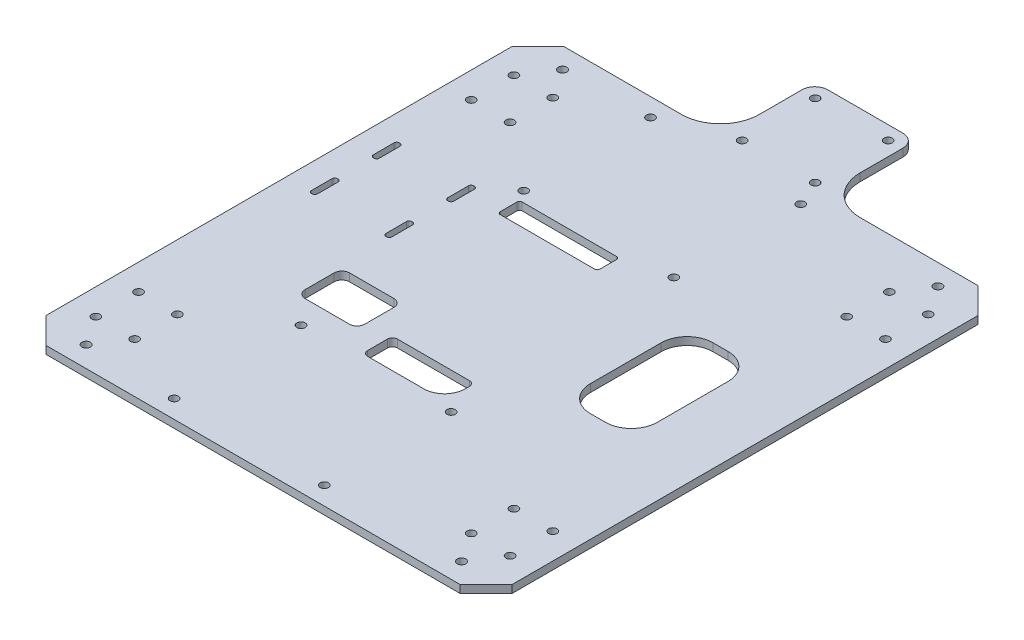
SolidWorks part; units mm, degrees
ref_plane "Front Plane" through (0, 0, 0) normal (0, 0, 1) x (1, 0, 0)
ref_plane "Top Plane" through (0, 0, 0) normal (0, 1, 0) x (1, 0, 0)
ref_plane "Right Plane" through (0, 0, 0) normal (1, 0, 0) x (0, 0, -1)
sketch "Sketch1" plane through (0, 0, 0) normal (0, 1, 0) x (1, 0, 0)
  line L0 (0, 132.1036) -> (0, -142.6838) construction
  line L1 (-90, 100) -> (90, 100)
  line L2 (-90, 100) -> (-90, -100)
  line L3 (-90, -100) -> (90, -100)
  line L4 (90, 100) -> (90, -100)
  line L5 (-90, 100) -> (90, -100) construction
  line L6 (-90, -100) -> (90, 100) construction
  line L7 (0, -55) -> (0, 55) construction
  line L8 (-189.9448, 0) -> (195.6261, 0) construction
  line L9 (18.5, 87.6829) -> (18.5, -193.4849) construction
  line L10 (-39.5, 87.6829) -> (-39.5, -193.4849) construction
  circle A0 centre (18.5, 93) radius 1.6
  circle A1 centre (18.5, 44) radius 1.6
  circle A2 centre (-39.5, 93) radius 1.6
  circle A3 centre (-39.5, 44) radius 1.6
  circle A9 centre (20.5, -93) radius 1.6
  circle A10 centre (20.5, -44) radius 1.6
  circle A11 centre (-37.5, -44) radius 1.6
  circle A12 centre (-37.5, -93) radius 1.6
  point P0 (0, 0)
  dimension "D3" = 58
  dimension "D4" = 3.2
  dimension "D5" = 3.2
  dimension "D6" = 49
  dimension "D7" = 7
  dimension "D8" = 58
  dimension "D9" = 18.5
  dimension "D10" = 18.5
  dimension "D11" = 39.5
  dimension "D12" = 49
  dimension "D13" = 3.2
  dimension "D14" = 3.2
  dimension "D15" = 3.2
  dimension "D16" = 7
  dimension "D17" = 2
  dimension "D18" = 3.2
  dimension "D19" = 49
  dimension "D20" = 20.5
  dimension "D21" = 58
  dimension "D22" = 3.2
  dimension "D23" = 3.2
  dimension "D24" = 49
  dimension "D25" = 58
  dimension "D26" = 37.5
  dimension "D1" = 180
  dimension "D2" = 200
extrude "Boss-Extrude1" add sketch "Sketch1" along normal blind 3
sketch "Sketch2" plane through (0, 3, 0) normal (0, 1, 0) x (1, 0, 0)
  line L0 (-162.8834, 0) -> (150.0475, 0) construction
  line L1 (0, 129.9084) -> (0, -141.4164) construction
  line L3 (-14.1809, -29.9956) -> (13.5, -29.9956)
  line L4 (-16.1809, -31.9956) -> (-16.1809, -39.5537)
  line L5 (-14.1809, -41.5537) -> (7.5, -41.5537)
  line L6 (15.5, -31.9956) -> (15.5, -33.5537)
  line L7 (-36.0134, 39.9424) -> (0.4565, 39.9424)
  line L8 (-37.0134, 38.9424) -> (-37.0134, 32.4822)
  line L9 (-36.0134, 31.4822) -> (0.4565, 31.4822)
  line L10 (1.4565, 38.9424) -> (1.4565, 32.4822)
  line L11 (-45.6227, -17.1125) -> (-28.5341, -17.1125)
  line L12 (-48.6227, -20.1125) -> (-48.6227, -31.2965)
  line L13 (-45.6227, -34.2965) -> (-28.5341, -34.2965)
  line L14 (-25.5341, -20.1125) -> (-25.5341, -31.2965)
  arc A0 (15.5, -31.9956) -> (13.5, -29.9956) centre (13.5, -31.9956) ccw
  arc A1 (-14.1809, -41.5537) -> (-16.1809, -39.5537) centre (-14.1809, -39.5537) cw
  arc A2 (-16.1809, -31.9956) -> (-14.1809, -29.9956) centre (-14.1809, -31.9956) cw
  arc A3 (7.5, -41.5537) -> (15.5, -33.5537) centre (7.5, -33.5537) ccw
  arc A4 (0.4565, 39.9424) -> (1.4565, 38.9424) centre (0.4565, 38.9424) cw
  arc A5 (0.4565, 31.4822) -> (1.4565, 32.4822) centre (0.4565, 32.4822) ccw
  arc A6 (-36.0134, 31.4822) -> (-37.0134, 32.4822) centre (-36.0134, 32.4822) cw
  arc A7 (-37.0134, 38.9424) -> (-36.0134, 39.9424) centre (-36.0134, 38.9424) cw
  circle A8 centre (20.5, -44) radius 1.6 construction
  arc A9 (-25.5341, -20.1125) -> (-28.5341, -17.1125) centre (-28.5341, -20.1125) ccw
  arc A10 (-28.5341, -34.2965) -> (-25.5341, -31.2965) centre (-28.5341, -31.2965) ccw
  arc A11 (-45.6227, -34.2965) -> (-48.6227, -31.2965) centre (-45.6227, -31.2965) cw
  arc A12 (-48.6227, -20.1125) -> (-45.6227, -17.1125) centre (-45.6227, -20.1125) cw
  dimension "D1" = 2
  dimension "D2" = 8
  dimension "D3" = 1
  dimension "D5" = 5
  dimension "D4" = 3
extrude "Cut-Extrude1" cut sketch "Sketch2" against normal up to surface (3 mm away) up to face at (0, 0, 0)
sketch "Sketch3" plane through (0, 3, 0) normal (0, 1, 0) x (1, 0, 0)
  line L0 (90, -100) -> (90, 100) construction
  line L1 (0, 125.5002) -> (0, -134.5016) construction
  line L2 (-137.7639, 0) -> (136.9662, 0) construction
  line L3 (-55, 0) -> (55, 0) construction
  line L4 (90, 100) -> (-90, 100) construction
  line L5 (80, 80.75) -> (80, 64.25) construction
  line L6 (80, 72.5) -> (90.3323, 72.5) construction
  line L7 (0, -55) -> (0, 55) construction
  line L8 (-80, 80.75) -> (-80, 64.25) construction
  line L9 (-80, 72.5) -> (-90.3323, 72.5) construction
  line L10 (80, -80.75) -> (80, -64.25) construction
  line L11 (80, -72.5) -> (90.3323, -72.5) construction
  line L12 (-80, -80.75) -> (-80, -64.25) construction
  line L13 (-80, -72.5) -> (-90.3323, -72.5) construction
  line L15 (-90, 100) -> (-90, -100) construction
  circle A0 centre (80, 80.75) radius 1.6
  circle A1 centre (65, 80.75) radius 1.6
  circle A2 centre (65, 64.25) radius 1.6
  circle A3 centre (80, 64.25) radius 1.6
  circle A4 centre (-80, 64.25) radius 1.6
  circle A5 centre (-65, 64.25) radius 1.6
  circle A6 centre (-65, 80.75) radius 1.6
  circle A7 centre (-80, 80.75) radius 1.6
  circle A8 centre (-80, -80.75) radius 1.6
  circle A9 centre (-65, -80.75) radius 1.6
  circle A10 centre (-65, -64.25) radius 1.6
  circle A11 centre (-80, -64.25) radius 1.6
  circle A12 centre (80, -64.25) radius 1.6
  circle A13 centre (65, -64.25) radius 1.6
  circle A14 centre (65, -80.75) radius 1.6
  circle A15 centre (80, -80.75) radius 1.6
  dimension "D1" = 3.2
  dimension "D2" = 10
  dimension "D3" = 3.2
  dimension "D4" = 15
  dimension "D6" = 16.5
  dimension "D7" = 19.25
  dimension "D8" = 25
  dimension "D9" = 180.6646
  dimension "D5" = 2
sketch "Sketch4" plane through (0, 3, 0) normal (0, 1, 0) x (1, 0, 0)
  line L5 (0, 125.5002) -> (0, -134.5016) construction
  line L6 (0, 147.4469) -> (0, 90.5728) construction
  line L7 (20.1578, 117.1) -> (-23.4234, 117.1) construction
  line L12 (90, 100) -> (-90, 100) construction
  line L13 (-19.5, 100) -> (19.5, 100)
  line L14 (-19.5, 115) -> (-19.5, 136.5)
  line L15 (-19.5, 136.5) -> (19.5, 136.5)
  line L16 (19.5, 115) -> (19.5, 136.5)
  line L17 (34.5, 100) -> (19.5, 100)
  line L18 (-34.5, 100) -> (-19.5, 100)
  circle A0 centre (14.1, 103) radius 1.6
  circle A1 centre (-14.1, 103) radius 1.6
  circle A2 centre (14.1, 131.2) radius 1.6
  circle A3 centre (-14.1, 131.2) radius 1.6
  arc A4 (19.5, 115) -> (34.5, 100) centre (34.5, 115) ccw
  arc A5 (-19.5, 115) -> (-34.5, 100) centre (-34.5, 115) cw
  dimension "D4" = 3.2
  dimension "D5" = 15
  dimension "D7" = 28.2
  dimension "D9" = 28.2
  dimension "D2" = 36.5
  dimension "D3" = 19.5
extrude "Boss-Extrude2" add sketch "Sketch4" against normal up to surface (3 mm away) up to face at (-17.7785, 0, -35.7123)
extrude "Cut-Extrude2" cut sketch "Sketch3" against normal through all
sketch "Sketch5" plane through (0, 3, 0) normal (0, 1, 0) x (1, 0, 0)
  line L0 (-119.2376, 0) -> (145.54, 0) construction
  line L1 (-65.0269, 34.8534) -> (-65.0269, 2.369) construction
  line L2 (-79.5488, 35.9861) -> (-79.2488, 35.9861)
  line L3 (-80.5488, 34.9861) -> (-80.5488, 26.9861)
  line L4 (-79.5488, 25.9861) -> (-79.2488, 25.9861)
  line L5 (-78.2488, 34.9861) -> (-78.2488, 26.9861)
  line L6 (-80.5488, 35.9861) -> (-78.2488, 25.9861) construction
  line L7 (-80.5488, 25.9861) -> (-78.2488, 35.9861) construction
  line L8 (-82.0133, 19.0367) -> (-45.889, 19.0367) construction
  line L9 (-49.505, 34.9861) -> (-49.505, 26.9861)
  line L10 (-51.805, 34.9861) -> (-51.805, 26.9861)
  line L11 (-51.805, 3.0873) -> (-51.805, 11.0873)
  line L12 (-49.505, 3.0873) -> (-49.505, 11.0873)
  line L13 (-78.2488, 3.0873) -> (-78.2488, 11.0873)
  line L14 (-79.5488, 12.0873) -> (-79.2488, 12.0873)
  line L15 (-80.5488, 3.0873) -> (-80.5488, 11.0873)
  line L16 (-79.5488, 2.0873) -> (-79.2488, 2.0873)
  line L17 (-50.505, 25.9861) -> (-50.805, 25.9861)
  line L18 (-50.505, 35.9861) -> (-50.805, 35.9861)
  line L19 (-50.505, 2.0873) -> (-50.805, 2.0873)
  line L20 (-50.505, 12.0873) -> (-50.805, 12.0873)
  arc A0 (-79.2488, 35.9861) -> (-78.2488, 34.9861) centre (-79.2488, 34.9861) cw
  arc A1 (-80.5488, 34.9861) -> (-79.5488, 35.9861) centre (-79.5488, 34.9861) cw
  arc A2 (-78.2488, 26.9861) -> (-79.2488, 25.9861) centre (-79.2488, 26.9861) cw
  arc A3 (-80.5488, 26.9861) -> (-79.5488, 25.9861) centre (-79.5488, 26.9861) ccw
  arc A4 (-51.805, 26.9861) -> (-50.805, 25.9861) centre (-50.805, 26.9861) ccw
  arc A5 (-49.505, 26.9861) -> (-50.505, 25.9861) centre (-50.505, 26.9861) cw
  arc A6 (-50.805, 35.9861) -> (-51.805, 34.9861) centre (-50.805, 34.9861) ccw
  arc A7 (-49.505, 34.9861) -> (-50.505, 35.9861) centre (-50.505, 34.9861) ccw
  arc A8 (-49.505, 3.0873) -> (-50.505, 2.0873) centre (-50.505, 3.0873) cw
  arc A9 (-50.805, 2.0873) -> (-51.805, 3.0873) centre (-50.805, 3.0873) cw
  arc A10 (-49.505, 11.0873) -> (-50.505, 12.0873) centre (-50.505, 11.0873) ccw
  arc A11 (-51.805, 11.0873) -> (-50.805, 12.0873) centre (-50.805, 11.0873) cw
  arc A12 (-80.5488, 11.0873) -> (-79.5488, 12.0873) centre (-79.5488, 11.0873) cw
  arc A13 (-78.2488, 11.0873) -> (-79.2488, 12.0873) centre (-79.2488, 11.0873) ccw
  arc A14 (-80.5488, 3.0873) -> (-79.5488, 2.0873) centre (-79.5488, 3.0873) ccw
  arc A15 (-79.2488, 2.0873) -> (-78.2488, 3.0873) centre (-79.2488, 3.0873) ccw
  point P3 (-79.3988, 30.9861)
  point P61 (-79.3988, 7.0873)
  dimension "D3" = 1
  dimension "D1" = 10
  dimension "D2" = 2.3
extrude "Cut-Extrude3" cut sketch "Sketch5" against normal through all
sketch "Sketch6" plane through (0, 3, 0) normal (0, 1, 0) x (1, 0, 0)
  line L0 (90, 100) -> (34.5, 100) construction
  line L1 (0, 159.522) -> (0, -147.3384) construction
  line L2 (-99.4598, 0) -> (104.7768, 0) construction
  circle A0 centre (72.5, 92) radius 1.65
  circle A1 centre (80, 80.75) radius 1.6 construction
  circle A4 centre (-72.5, 92) radius 1.65
  circle A5 centre (72.5, -92) radius 1.65
  circle A6 centre (-72.5, -92) radius 1.65
  dimension "D1" = 3.3
  dimension "D2" = 7.5
  dimension "D3" = 8
extrude "Cut-Extrude4" cut sketch "Sketch6" against normal through all
sketch "Sketch7" plane through (0, 3, 0) normal (0, 1, 0) x (1, 0, 0)
  line L1 (47.9236, 29.7083) -> (53.7866, 29.7083)
  line L2 (37.9236, 19.7083) -> (37.9236, -7.6655)
  line L3 (47.9236, -17.6655) -> (53.7866, -17.6655)
  line L4 (63.7866, 19.7083) -> (63.7866, -7.6655)
  arc A0 (63.7866, 19.7083) -> (53.7866, 29.7083) centre (53.7866, 19.7083) ccw
  arc A1 (53.7866, -17.6655) -> (63.7866, -7.6655) centre (53.7866, -7.6655) ccw
  arc A2 (47.9236, -17.6655) -> (37.9236, -7.6655) centre (47.9236, -7.6655) cw
  arc A3 (37.9236, 19.7083) -> (47.9236, 29.7083) centre (47.9236, 19.7083) cw
  dimension "D1" = 10
extrude "Cut-Extrude5" cut sketch "Sketch7" against normal through all
chamfer "Chamfer1" distance 10 angle 45 4 edges at (-90, 1.5, 100) (90, 1.5, 100) (-90, 1.5, -100) (90, 1.5, -100)
fillet "Fillet1" radius 5 2 edges at (19.5, 1.5, -136.5) (-19.5, 1.5, -136.5)
